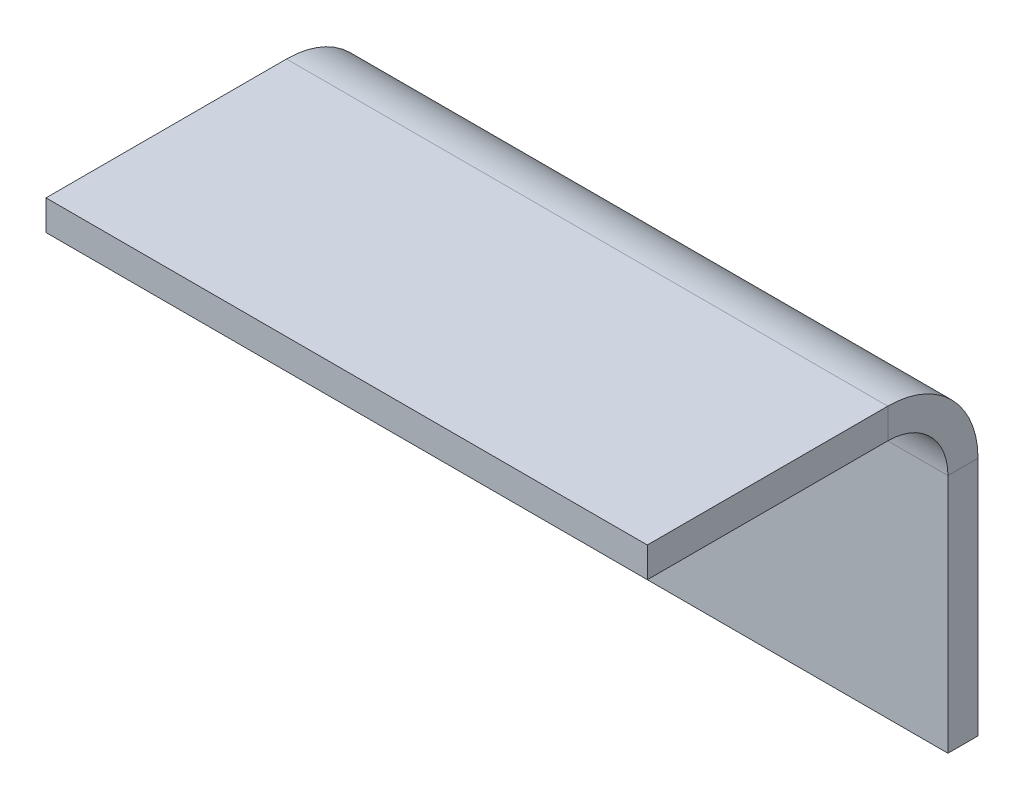
SolidWorks part; units mm, degrees
note: The reader was unsure of these and kept them because the rebuilt part matched: flange length of "EdgeFlange".
ref_plane "前视基准面" through (0, 0, 0) normal (0, 0, 1) x (1, 0, 0)
ref_plane "上视基准面" through (0, 0, 0) normal (0, 1, 0) x (1, 0, 0)
ref_plane "右视基准面" through (0, 0, 0) normal (1, 0, 0) x (0, 0, -1)
other "Configuration Table"
sketch "草图1" plane through (0, 0, 0) normal (0, 0, 1) x (1, 0, 0)
  line L1 (0, 0) -> (20, 0)
  line L2 (0, 0) -> (0, 10)
  line L3 (0, 10) -> (20, 10)
  line L4 (20, 0) -> (20, 10)
base flange "BasePlate" sketch "草图1" thickness 1 reverse thickness direction no parameters "D1"=2
sketch "草图9" plane through (0, 10, 0) normal (0, 1, 0) x (-1, 0, 0)
  line L0 (-20, 0) -> (0, 0) construction
  line L1 (-20, 0) -> (0, 0)
  line L2 (-20, 0) -> (-20, 10)
  line L3 (-20, 10) -> (-18, 10)
  line L4 (-18, 10) -> (-2, 10)
  line L5 (-2, 10) -> (0, 10)
  line L6 (0, 0) -> (0, 10)
edge flange "EdgeFlange" sketch "草图9" flange angle 90 flange length 10 flange position material outside bend radius 2 thickness 1 relief rectangular parameters "D6"=10
bend "边线折弯1" bend radius 2 bend angle 90 parameters "D5"=1
sketch "折弯-线1" plane through (0, 0, 0) normal (0, 1, 0) x (1, 0, 0)
sketch "边界框1" plane through (0, 0, 0) normal (0, 1, 0) x (1, 0, 0)
sheet metal parameters "钣金6" thickness 1 parameters "D1"=2
flat pattern "平板型式6" [suppressed]
sketch "折弯-线2" plane through (0, 0, 0) normal (0, 1, 0) x (1, 0, 0)
sketch "边界框2" [suppressed] plane through (0, 0, 0) normal (0, 1, 0) x (1, 0, 0)
sheet metal parameters "钣金7" thickness 1 parameters "D1"=2
flat pattern "平板型式6" [suppressed]
sketch "折弯-线2" plane through (0, 0, 0) normal (0, 1, 0) x (1, 0, 0)
sketch "边界框2" [suppressed] plane through (0, 0, 0) normal (0, 1, 0) x (1, 0, 0)
bend of the flat pattern "展平-<边线折弯1>1"
